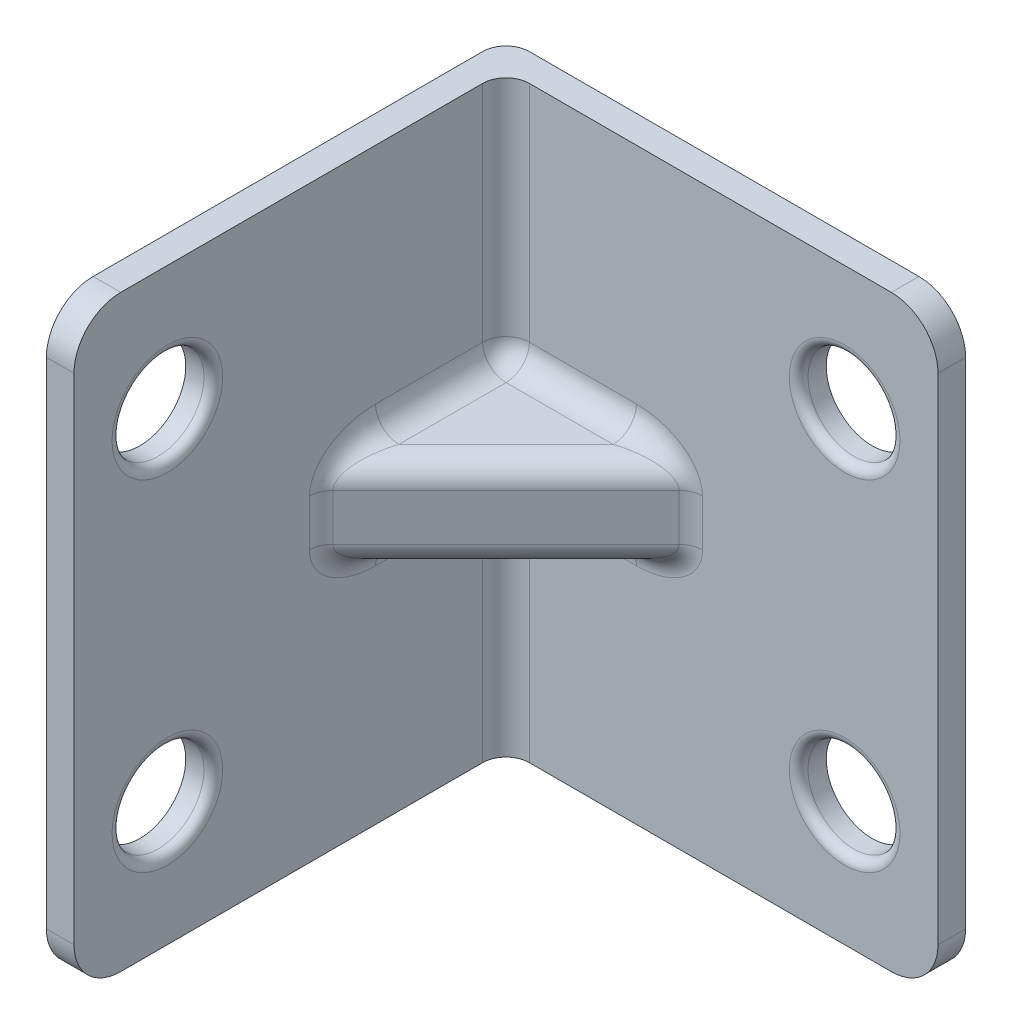
SolidWorks part; units mm, degrees
ref_plane "Front Plane" through (0, 0, 0) normal (0, 0, 1) x (1, 0, 0)
ref_plane "Top Plane" through (0, 0, 0) normal (0, 1, 0) x (1, 0, 0)
ref_plane "Right Plane" through (0, 0, 0) normal (1, 0, 0) x (0, 0, -1)
sketch "Sketch1" plane through (0, 0, 0) normal (0, 0, 1) x (1, 0, 0)
  line L0 (12.5, 0) -> (-12.5, 0) construction
  line L1 (-12.5, 16) -> (12.5, 16) construction
  line L2 (-12.5, 16) -> (-12.5, -16) construction
  line L3 (-12.5, -16) -> (12.5, -16) construction
  line L4 (12.5, 16) -> (12.5, -16) construction
  line L5 (-12.5, 16) -> (12.5, -16) construction
  line L6 (-12.5, -16) -> (12.5, 16) construction
  line L8 (-12.5, 16) -> (-12.5, -16)
  line L9 (-12.5, -16) -> (12.5, -16)
  line L10 (-12.5, 16) -> (12.5, 16)
  line L11 (12.5, 16) -> (12.5, -16)
  line L12 (7.42, 9.25) -> (7.42, -9.25) construction
  circle A3 centre (7.42, -9.25) radius 2.5
  circle A4 centre (7.42, 9.25) radius 2.5
  point P7 (0, 0)
  point P10 (7.42, 0)
  dimension "D1" = 18.5
  dimension "D4" = 5
  dimension "D5" = 5
  dimension "D2" = 25
  dimension "D3" = 32
  dimension "D6" = 5.08
extrude "Boss-Extrude1" add sketch "Sketch1" along normal blind 1.5
sketch "Sketch2" plane through (-12.5, 0, 0) normal (-1, 0, 0) x (0, 0, 1)
  line L0 (1.5, 16) -> (0, 16) construction
  line L1 (0, -16) -> (25, -16)
  line L2 (0, -16) -> (0, 16)
  line L3 (0, 16) -> (25, 16)
  line L4 (25, -16) -> (25, 16)
  line L5 (0, -16) -> (25, 16) construction
  line L6 (0, 16) -> (25, -16) construction
  line L7 (25, 0) -> (0, 0) construction
  line L8 (19.92, -9.25) -> (19.92, 9.25) construction
  circle A0 centre (19.92, -9.25) radius 2.5
  circle A1 centre (19.92, 9.25) radius 2.5
  point P4 (12.5, 0)
  point P12 (19.92, 0)
  dimension "D4" = 5
  dimension "D5" = 5
  dimension "D1" = 25
  dimension "D2" = 18.5
  dimension "D3" = 5.08
extrude "Boss-Extrude2" add sketch "Sketch2" against normal blind 1.5
sketch "Sketch3" plane through (0, 0, 0) normal (0, 1, 0) x (1, 0, 0)
  line L0 (-11, -25) -> (-11, -1.5) construction
  line L1 (-11, -25) -> (-11, -1.5) construction
  line L2 (12.5, -1.5) -> (-11, -1.5) construction
  line L3 (12.5, -1.5) -> (-11, -1.5) construction
  line L4 (-11, -1.5) -> (-11, -11.66)
  line L5 (-11, -11.66) -> (-0.84, -1.5)
  line L6 (-0.84, -1.5) -> (-11, -1.5)
  dimension "D1" = 45
  dimension "D2" = 10.16
extrude "Boss-Extrude3" add sketch "Sketch3" along normal blind 2.54 and the other way blind 2.54
fillet "Fillet1" radius 1.27 10 edges at (-11, 0, 11.66) (-0.84, 0, 1.5) (-11, -2.54, 6.58) (-5.92, -2.54, 6.58) (-5.92, -2.54, 1.5) (-5.92, 2.54, 6.58) (-11, 2.54, 6.58) (-5.92, 2.54, 1.5) (-11, 9.27, 1.5) (-11, -9.27, 1.5)
fillet "Fillet2" radius 1.27 1 edges at (-12.5, 0, 0)
fillet "Fillet3" radius 0.508 4 edges at (-11, 6.75, 19.92) (-11, -11.75, 19.92) (9.92, -9.25, 1.5) (9.92, 9.25, 1.5)
fillet "Fillet4" radius 2.54 4 edges at (12.5, -16, 0.75) (-11.75, -16, 25) (-11.75, 16, 25) (12.5, 16, 0.75)
